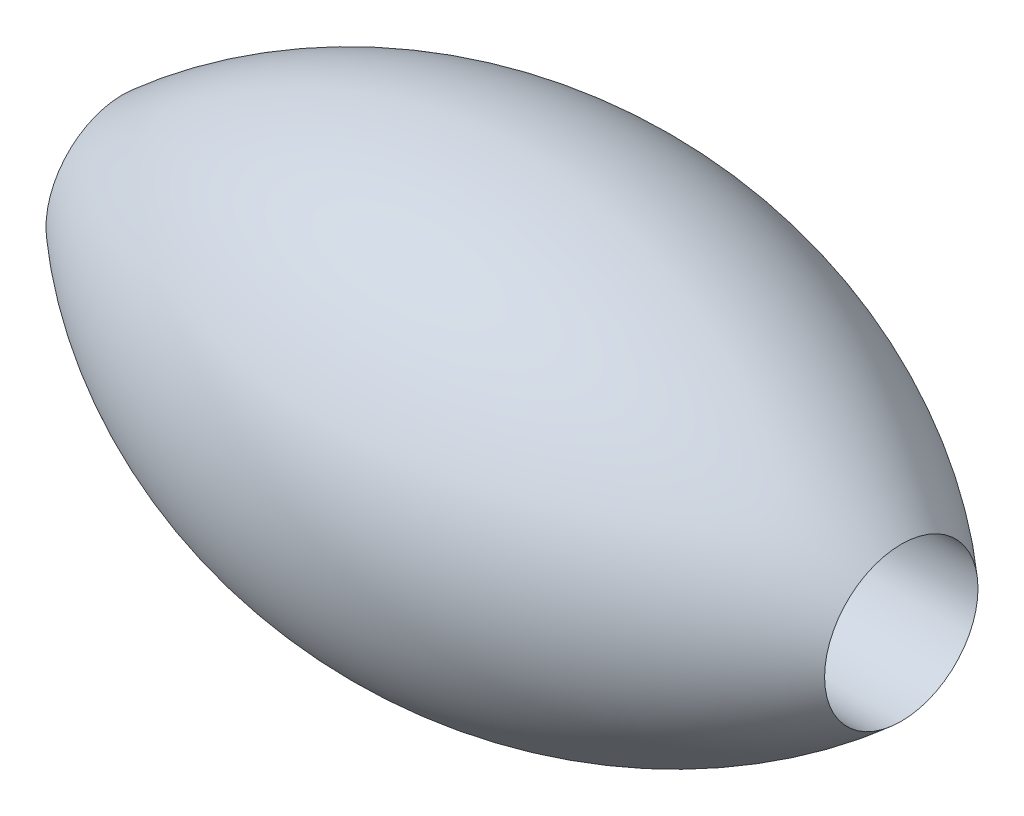
SolidWorks part; units mm, degrees
ref_plane "Front Plane" through (0, 0, 0) normal (0, 0, 1) x (1, 0, 0)
ref_plane "Top Plane" through (0, 0, 0) normal (0, 1, 0) x (1, 0, 0)
ref_plane "Right Plane" through (0, 0, 0) normal (1, 0, 0) x (0, 0, -1)
sketch "Olive Tip" plane through (0, 0, 0) normal (0, 0, 1) x (1, 0, 0)
  line L0 (-5.537, 0) -> (0.813, 0)
  line L1 (-2.362, 0) -> (-2.362, -1.5367)
  line L2 (3.3, 0) -> (-3.3, 0) construction
  arc A0 (0.813, 0) -> (-5.537, 0) centre (-2.362, 2.5116) cw
  point P7 (-2.362, 0)
  dimension "D1" = 1.5367
  dimension "D2" = 6.35
revolve "MainBody" add sketch "Olive Tip" angle 360 about L0
sketch "Inner Diameter" plane through (0, 0, 0) normal (1, 0, 0) x (0, 0, -1)
  circle A0 centre (0, 0) radius 0.5271
  dimension "D1" = 1.0541
extrude "Inner Lumen" cut sketch "Inner Diameter" against normal through all and the other way through all
equation "\"olive_max_diameter\" = 0.121in / 2"
equation "\"D1@Olive Tip\"=\"olive_max_diameter\""
equation "\"olive_length\" = 0.25in"
equation "\"D2@Olive Tip\"=\"olive_length\""
equation "\"olive_ID\"= 0.0415in"
equation "\"D1@Inner Diameter\"=\"olive_ID\""
